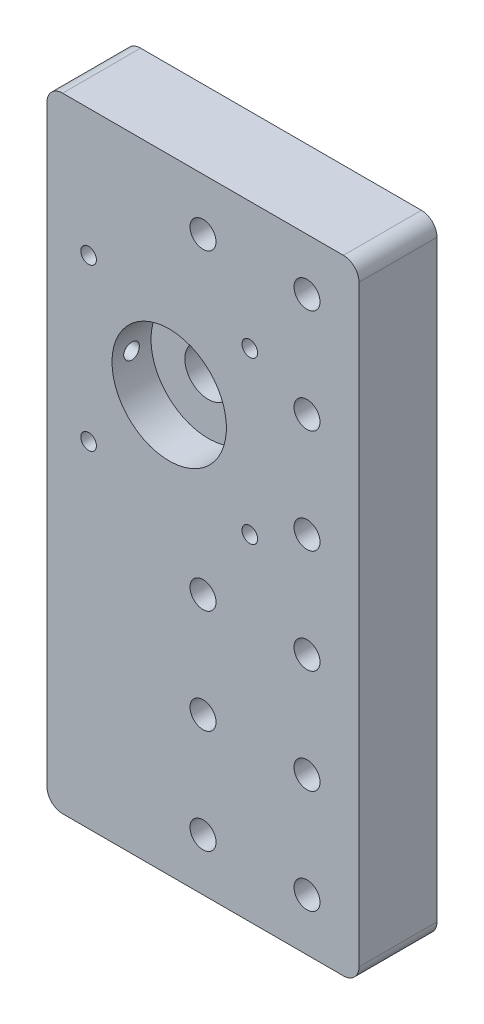
SolidWorks part; units mm, degrees
ref_plane "Płaszczyzna przednia" through (0, 0, 0) normal (0, 0, 1) x (1, 0, 0)
ref_plane "Płaszczyzna górna" through (0, 0, 0) normal (0, 1, 0) x (1, 0, 0)
ref_plane "Płaszczyzna prawa" through (0, 0, 0) normal (1, 0, 0) x (0, 0, -1)
sketch "Sketch1" plane through (0, 0, 0) normal (0, 0, 1) x (1, 0, 0)
  line L0 (72.0964, 110) -> (-17.7275, 110) construction
  line L1 (0, 0) -> (60, 0)
  line L2 (0, 0) -> (0, 120)
  line L3 (0, 120) -> (60, 120)
  line L4 (60, 0) -> (60, 120)
  line L5 (10, 111.3456) -> (10, -27.1164) construction
  line L6 (-17.7275, 10) -> (75.4304, 10) construction
  line L7 (-17.7275, 50) -> (77.7275, 50) construction
  circle A0 centre (10, 110) radius 2.5
  circle A1 centre (30, 110) radius 2.5
  circle A2 centre (10, 90) radius 2.5
  circle A3 centre (10, 70) radius 2.5
  circle A5 centre (10, 10) radius 2.5
  circle A6 centre (30, 10) radius 2.5
  circle A8 centre (30, 50) radius 2.5
  circle A9 centre (10, 50) radius 2.5
  circle A10 centre (10, 30) radius 2.5
  circle A11 centre (30, 30) radius 2.5
  dimension "D11" = 5
  dimension "D1" = 120
  dimension "D2" = 60
  dimension "D3" = 10
  dimension "D4" = 10
  dimension "D5" = 10
  dimension "D6" = 20
  dimension "D7" = 20
  dimension "D8" = 20
  dimension "D9" = 20
  dimension "D10" = 20
  dimension "D12" = 20
extrude "Boss-Extrude1" add sketch "Sketch1" along normal blind 15
fillet "Fillet1" radius 3 4 edges at (0, 0, 7.5) (60, 0, 7.5) (0, 120, 7.5) (60, 120, 7.5)
sketch "Sketch2" plane through (0, 0, 15) normal (0, 0, 1) x (1, 0, 0)
  line L0 (45.9963, 120) -> (36.5, 120) construction
  line L1 (57, 120) -> (3, 120) construction
  line L2 (36.5, 120) -> (36.5, 0) construction
  line L3 (3, 0) -> (57, 0) construction
  line L4 (0, 117) -> (0, 3) construction
  line L5 (0, 80) -> (60, 80) construction
  line L6 (60, 3) -> (60, 117) construction
  circle A0 centre (10, 70) radius 2.5 construction
  circle A1 centre (10, 90) radius 2.5 construction
  circle A2 centre (36.5, 80) radius 11
  circle A3 centre (21, 95.5) radius 1.5
  circle A4 centre (52, 95.5) radius 1.5
  circle A5 centre (52, 64.5) radius 1.5
  circle A6 centre (21, 64.5) radius 1.5
  circle A7 centre (36.5, 80) radius 4.5
  dimension "D4" = 3
  dimension "D5" = 22
  dimension "D6" = 9
  dimension "D1" = 36.5
  dimension "D2" = 31
  dimension "D3" = 31
extrude "Cut-Extrude1" cut sketch "Sketch2" against normal through all contours A7 | A4 | A3 | A5 | A6 region at (21, 95.5, 15) region at (52, 95.5, 15) region at (52, 64.5, 15) region at (36.5, 80, 15)
extrude "Cut-Extrude2" cut sketch "Sketch2<3>" against normal blind 7.5 contours A2 A7 region at (25.8111, 80, 15)
sketch "Sketch2<3>" plane through (0, 0, 15) normal (0, 0, 1) x (1, 0, 0) same geometry as "Sketch2"
mirror "Mirror1" about plane through (60, 0, 15) normal (-1, 0, 0) of bodies 103
delete or keep bodies "Body-Delete/Keep 1" type delete bodies bodies 103
sketch "Sketch3" plane through (60, 0, 0) normal (-1, 0, 0) x (0, 0, 1)
  line L0 (15, 80) -> (7.5, 80) construction
  line L1 (15, 69) -> (15, 91) construction
  line L2 (7.5, 69) -> (7.5, 91) construction
  circle A0 centre (11.25, 80) radius 1.5
  dimension "D1" = 3
extrude "Cut-Extrude3" cut sketch "Sketch3" against normal up to next
